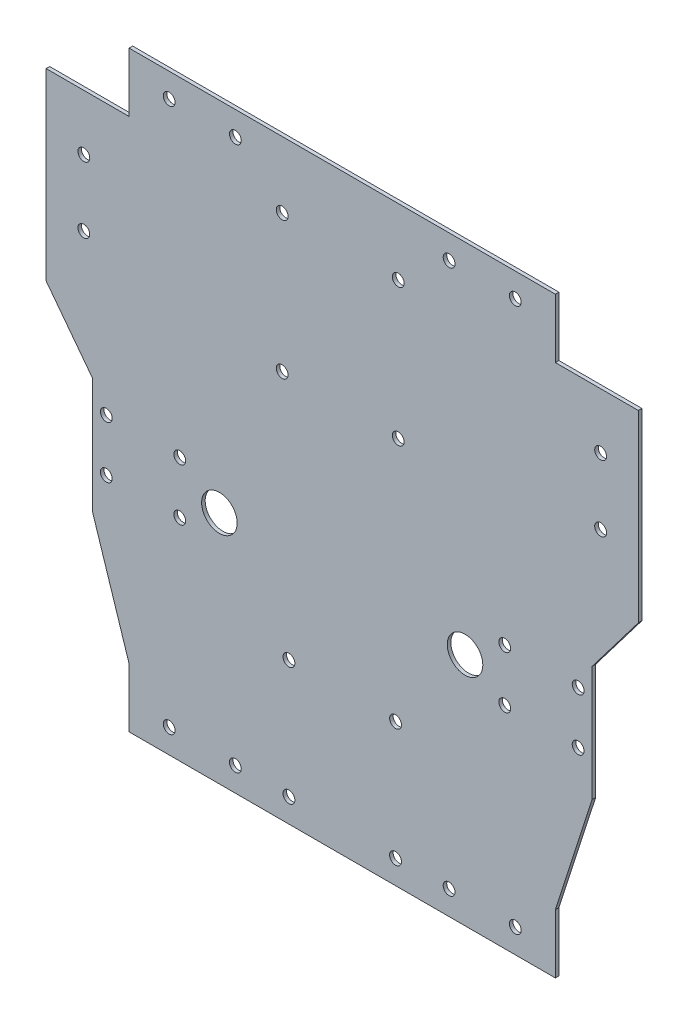
SolidWorks part; units mm, degrees
other "Markup1"
sketch "Sketch7" plane through (25, 0, 0) normal (-0.133, -0.1918, 0.9724) x (0.9904, 0.0125, 0.1379)
material "6061 Alloy"
ref_plane "Front Plane" through (0, 0, 0) normal (0, 0, 1) x (1, 0, 0)
ref_plane "Top Plane" through (0, 0, 0) normal (0, 1, 0) x (1, 0, 0)
ref_plane "Right Plane" through (0, 0, 0) normal (1, 0, 0) x (0, 0, -1)
sketch "Sketch1" plane through (0, 0, 0) normal (0, 0, 1) x (1, 0, 0)
  line L1 (0, 0) -> (300, 0)
  line L2 (0, 0) -> (0, 250)
  line L3 (0, 250) -> (300, 250)
  line L4 (300, 0) -> (300, 250)
  dimension "D1" = 300
  dimension "D2" = 250
extrude "Boss-Extrude1" add sketch "Sketch1" against normal blind 1.5
sketch "Motor Center Line" plane through (0, 0, -1.5) normal (0, 0, -1) x (-1, 0, 0)
  line L0 (0, 100) -> (-300, 100) construction
  line L3 (-300, 250) -> (0, 250) construction
  dimension "D1" = 150
sketch "Sketch2" plane through (0, 0, 0) normal (0, 0, 1) x (1, 0, 0)
  line L0 (150, 0.825) -> (150, -0.825) construction
  line L1 (0, 0) -> (20, 0)
  line L2 (0, 0) -> (0, 20)
  line L3 (0, 20) -> (20, 20)
  line L4 (20, 0) -> (20, 20)
  line L5 (300, 20) -> (280, 20)
  line L6 (280, 0) -> (280, 20)
  line L7 (300, 0) -> (280, 0)
  line L8 (300, 0) -> (300, 20)
  line L10 (0, 125) -> (300, 125) construction
  line L11 (0, 250) -> (0, 0) construction
  line L12 (300, 0) -> (300, 250) construction
  line L13 (300, 250) -> (300, 230)
  line L14 (300, 250) -> (280, 250)
  line L15 (280, 250) -> (280, 230)
  line L16 (300, 230) -> (280, 230)
  line L17 (0, 230) -> (20, 230)
  line L18 (20, 250) -> (20, 230)
  line L19 (0, 250) -> (20, 250)
  line L20 (0, 250) -> (0, 230)
  dimension "D1" = 20
sketch "Sketch3" plane through (0, 0, 0) normal (0, 0, 1) x (1, 0, 0)
  line L0 (150, 250) -> (150, 0) construction
  line L1 (0, 0) -> (25, 0)
  line L2 (0, 0) -> (0, 25)
  line L3 (0, 25) -> (25, 25)
  line L4 (25, 0) -> (25, 25)
  line L5 (300, 250) -> (0, 250) construction
  line L6 (0, 0) -> (300, 0) construction
  line L7 (0, 125) -> (300, 125) construction
  line L8 (0, 250) -> (0, 0) construction
  line L9 (300, 0) -> (300, 250) construction
  line L10 (300, 25) -> (275, 25)
  line L11 (275, 0) -> (275, 25)
  line L12 (300, 0) -> (275, 0)
  line L13 (300, 0) -> (300, 25)
  line L14 (300, 250) -> (300, 225)
  line L15 (300, 250) -> (275, 250)
  line L16 (275, 250) -> (275, 225)
  line L17 (300, 225) -> (275, 225)
  line L18 (0, 225) -> (25, 225)
  line L19 (25, 250) -> (25, 225)
  line L20 (0, 250) -> (25, 250)
  line L21 (0, 250) -> (0, 225)
  line L22 (255.5, 73) -> (275, 47.3437)
  line L23 (255.5, 73) -> (255.5, 121.6874)
  line L24 (255.5, 121.6874) -> (275, 147.3437)
  line L25 (275, 147.3437) -> (300, 147.3437)
  line L26 (300, 147.3437) -> (300, 25)
  line L27 (275, 47.3437) -> (275, 25)
  line L28 (44.5, 73) -> (25, 47.3437)
  line L29 (25, 47.3437) -> (25, 25)
  line L30 (44.5, 73) -> (44.5, 121.6874)
  line L31 (265.5, 121.25) -> (265.5, 78.75) construction
  line L32 (44.5, 121.6874) -> (25, 147.3437)
  line L37 (287.5, 147.3437) -> (287.5, 225)
  line L38 (25, 147.3437) -> (0, 147.3437)
  line L39 (12.5, 147.3437) -> (12.5, 225)
  circle A0 centre (201.85, 99.1258) radius 7.5
  circle A1 centre (98.15, 99.1258) radius 7.5
  ellipse E4 centre (201.85, 99.7743) end of major axis (201.2, 99.7743) minor radius 0.6484 construction
  line M15 (0, 250) -> (0, 0)
  line M16 (0, 0) -> (300, 0)
  line M17 (300, 0) -> (300, 250)
  line M18 (300, 250) -> (0, 250)
  dimension "D3" = 15
  dimension "D1" = 25
  dimension "D2" = 10
  dimension "D4" = 100
extrude "Cut-Extrude1" cut sketch "Sketch3" against normal through all both and the other way through all contours L11 L10 M16 M17 | L25 L24 L23 L10 M17 | L17 L16 M17 M18 | L19 L18 M18 M15 | L3 M15 | L4 L3 M16 M15 | A1 | A0 | L18 M15 | L37 L25 L17 M17 region at (12.5, 12.5, 0) region at (19.2941, 89.7643, 0) region at (287.5, 12.5, 0) region at (6.25, 186.1719, 0) region at (280.7059, 89.7643, 0) region at (12.5, 237.5, 0) region at (293.75, 186.1719, 0) region at (287.5, 237.5, 0) region at (201.85, 99.1258, 0) region at (98.15, 99.1258, 0)
sketch "Sketch4" plane through (0, 0, 0) normal (0, 0, 1) x (1, 0, 0)
  arc A0 (174.9953, 164.0221) -> (172.2953, 164.0221) centre (173.6453, 164.0221) ccw construction
  arc A1 (125.9953, 164.0221) -> (123.2953, 164.0221) centre (124.6453, 164.0221) ccw construction
  arc A4 (125.9953, 222.0221) -> (123.2953, 222.0221) centre (124.6453, 222.0221) ccw construction
  arc A5 (174.9953, 222.0221) -> (172.2953, 222.0221) centre (173.6453, 222.0221) ccw construction
  point P0 (40.9169, 201.47)
  point P1 (40.9169, 173.53)
  point P3 (76.94, 239.84)
  point P4 (104.88, 239.84)
  point P5 (195.12, 239.84)
  point P9 (223.06, 239.84)
  point P11 (259.0831, 201.47)
  point P13 (259.0831, 173.53)
  point P15 (195.12, 10.16)
  point P17 (223.06, 10.16)
  point P19 (76.94, 10.16)
  point P21 (104.88, 10.16)
  point P23 (127.5, 10)
  point P25 (172.5, 10)
  point P27 (127.5, 60)
  point P29 (172.5, 60)
  point P31 (124.6453, 164.0221)
  point P33 (173.6453, 164.0221)
  point P35 (124.6453, 222.0221)
  point P37 (173.6453, 222.0221)
  point P39 (218.6, 111)
  point P41 (249.6, 111)
  point P43 (249.6, 89)
  point P45 (218.6, 89)
  point P47 (81.4, 89.0063)
  point P49 (50.4, 89.0063)
  point P51 (81.4, 111.0063)
  point P53 (50.4, 111.0063)
sketch "Sketch6" plane through (0, 0, 0) normal (0, 0, 1) x (1, 0, 0)
  line L1 (275, 0) -> (240, 0)
  line L2 (275, 0) -> (275, 25)
  line L3 (275, 25) -> (240, 25)
  line L4 (240, 0) -> (240, 25)
  line L5 (240, 25) -> (255.5, 73)
  line L6 (150, 250) -> (150, 0) construction
  line L7 (275, 250) -> (25, 250) construction
  line L8 (25, 0) -> (275, 0) construction
  line L9 (60, 25) -> (44.5, 73)
  line L10 (25, 25) -> (60, 25)
  line L11 (60, 0) -> (60, 25)
  line L12 (25, 0) -> (60, 0)
  line L13 (25, 0) -> (25, 25)
  line L14 (275, 250) -> (240, 250)
  line L15 (25, 225) -> (60, 225)
  line L16 (25, 225) -> (25, 250)
  line L17 (25, 250) -> (60, 250)
  line L18 (60, 225) -> (60, 250)
  line L19 (240, 225) -> (240, 250)
  line L20 (275, 225) -> (240, 225)
  line L21 (275, 225) -> (275, 250)
  line L22 (25, 225) -> (25, 147.3437)
  line L23 (275, 147.3437) -> (275, 225)
  line L24 (287.5, 225) -> (287.5, 147.3437)
  line L25 (287.5, 147.3437) -> (275, 147.3437)
  line L26 (25, 225) -> (12.5, 225)
  line L27 (12.5, 225) -> (12.5, 147.3437)
  line L28 (12.5, 147.3437) -> (25, 147.3437)
  line M11 (275, 0) -> (275, 47.3437)
  line M12 (275, 47.3437) -> (255.5, 73)
  line M15 (275, 147.3437) -> (287.5, 147.3437)
  line M16 (287.5, 147.3437) -> (287.5, 225)
  line M17 (287.5, 225) -> (275, 225)
  line M18 (275, 225) -> (275, 250)
  line M19 (275, 250) -> (25, 250)
  line M20 (25, 250) -> (25, 225)
  line M21 (25, 225) -> (12.5, 225)
  line M22 (12.5, 225) -> (12.5, 147.3437)
  line M23 (12.5, 147.3437) -> (25, 147.3437)
  line M26 (44.5, 73) -> (25, 47.3437)
  line M27 (25, 47.3437) -> (25, 0)
  line M28 (25, 0) -> (275, 0)
  dimension "D1" = 25
  dimension "D2" = 35
extrude "Cut-Extrude3" cut sketch "Sketch6" against normal through all contours L11 L10 M28 M27 | L10 L9 M27 M26 | L4 L3 M28 M11 | L5 L3 M11 M12 | L15 L18 M19 M20 | L20 L19 M18 M19 | L22 M21 M22 M23 | L23 M15 M16 M17 region at (42.5, 12.5, 0) region at (257.5, 12.5, 0) region at (259.2359, 42.5338, 0) region at (40.7641, 42.5338, 0) region at (257.5, 237.5, 0) region at (281.25, 186.1719, 0) region at (18.75, 186.1719, 0) region at (42.5, 237.5, 0)
sketch "Sketch5" plane through (0, 0, 0) normal (0, 0, 1) x (1, 0, 0)
  circle A0 centre (76.94, 10.16) radius 2.5
  dimension "D1" = 5
extrude "Cut-Extrude2" cut sketch "Sketch5" against normal through all both
pattern_sketch "Sketch-Pattern1" of "Cut-Extrude2" driven by "Sketch4"
